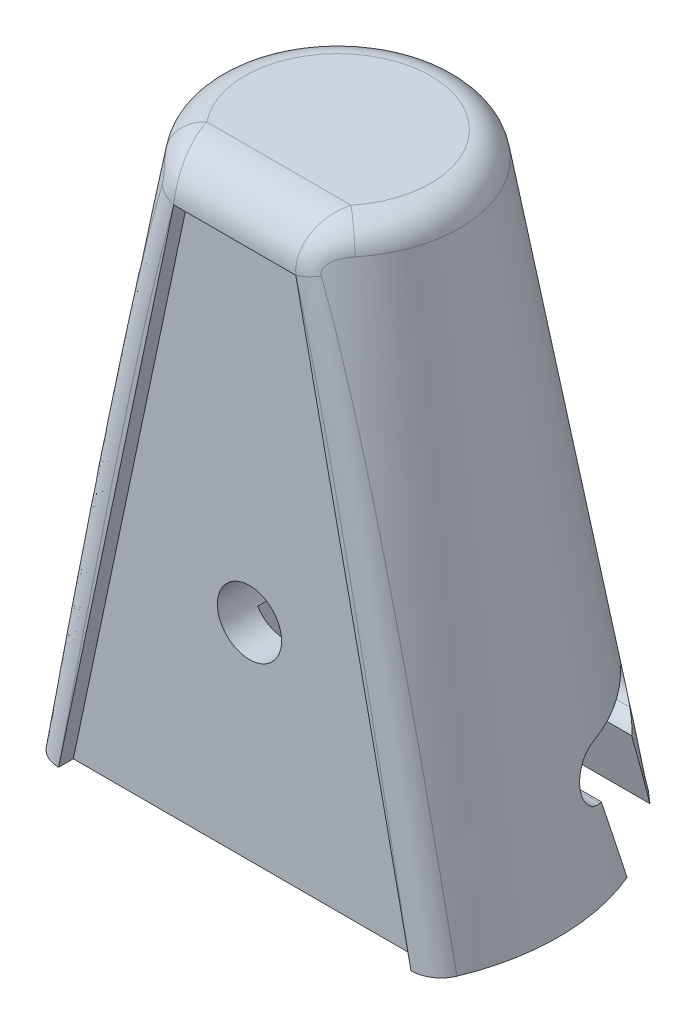
SolidWorks part; units mm, degrees
ref_plane "Front Plane" through (0, 0, 0) normal (0, 0, 1) x (1, 0, 0)
ref_plane "Top Plane" through (0, 0, 0) normal (0, 1, 0) x (1, 0, 0)
ref_plane "Right Plane" through (0, 0, 0) normal (1, 0, 0) x (0, 0, -1)
sketch "Sketch1" plane through (0, 0, 0) normal (0, 0, 1) x (1, 0, 0)
  line L0 (0, -20) -> (-7.5, -20)
  line L1 (-7.5, -20) -> (-4, 0)
  line L2 (-4, 0) -> (0, 0)
  line L3 (0, 0) -> (0, -20)
  dimension "D1" = 4
  dimension "D2" = 7.5
  dimension "D3" = 20
revolve "Revolve1" add sketch "Sketch1" angle 360 about L3
sketch "Sketch8" plane through (0, -20, 0) normal (0, -1, 0) x (1, 0, 0)
  line L3 (-0.9223, 1.8) -> (1.2577, 1.8)
  line L4 (-0.9223, 1.8) -> (-0.9223, -0.38)
  line L5 (-0.9223, -0.38) -> (1.2577, -0.38)
  line L6 (1.2577, 1.8) -> (1.2577, -0.38)
  dimension "D1" = 2.18
  dimension "D2" = 2.18
extrude "Cut-Extrude3" cut sketch "Sketch8" against normal blind 9
sketch "Sketch13" plane through (0, -20, 0) normal (0, -1, 0) x (1, 0, 0)
  line L0 (-6.6332, 3.5) -> (6.6332, 3.5)
  arc A0 (-6.6332, 3.5) -> (6.6332, 3.5) centre (0, 0) cw
  circle A1 centre (0, 0) radius 7.5 construction
  dimension "D1" = 3.5
  dimension "D2" = 3.5
extrude "Cut-Extrude5" cut sketch "Sketch13" against normal blind 20
fillet "Fillet2" radius 1.5 1 edges at (0, 0, 3.5)
fillet "Fillet3" radius 1 5 edges at (-2.5953, -0.5643, 3.1724) (2.4731, -0.7797, 3.3157) (0, 0, -4) (3.9921, -7.4806, 3.5) (-5.5122, -14.4545, 3.5)
sketch "Sketch15" plane through (0, 0, 0) normal (1, 0, 0) x (0, 0, -1)
  line L2 (2.2531, -15.9414) -> (4.7106, -15.9414)
  line L5 (2.2421, -17.5402) -> (2.913, -20)
  line L7 (-2.878, -20) -> (7.5, -20) construction
  line L8 (5.4729, -20) -> (4.7028, -17.5403)
  arc A0 (2.2421, -17.5402) -> (2.173, -17.5363) centre (2.2531, -16.7409) cw
  arc A1 (2.173, -17.5363) -> (2.2531, -15.9414) centre (2.2531, -16.7409) cw
  arc A2 (4.7106, -15.9414) -> (5.2781, -17.3039) centre (4.7106, -16.7409) cw
  arc A3 (5.2781, -17.3039) -> (4.7028, -17.5403) centre (4.7106, -16.7409) cw
  dimension "D2" = 0.7994
  dimension "D3" = 0.7994
  dimension "D5" = 0.7994
  dimension "D6" = 0.7994
extrude "Cut-Extrude7" cut sketch "Sketch15" against normal through all both and the other way through all
sketch "Sketch21" plane through (0, 0, 3.5) normal (0, 0, 1) x (1, 0, 0)
  line L0 (-2.0724, -1.5) -> (2.0724, -1.5)
  line L1 (2.0724, -1.5) -> (5.9835, -20)
  line L2 (5.9835, -20) -> (-5.9835, -20)
  line L3 (-5.9835, -20) -> (-2.0724, -1.5)
extrude "Cut-Extrude8" cut sketch "Sketch21" against normal blind 0.5
sketch "Sketch22" plane through (0, 0, 3) normal (0, 0, 1) x (1, 0, 0)
  line L0 (-5.9835, -20) -> (5.9835, -20) construction
  circle A0 centre (0, -13) radius 1.09
  dimension "D1" = 2.18
  dimension "D2" = 7
extrude "Cut-Extrude9" cut sketch "Sketch22" against normal through all
